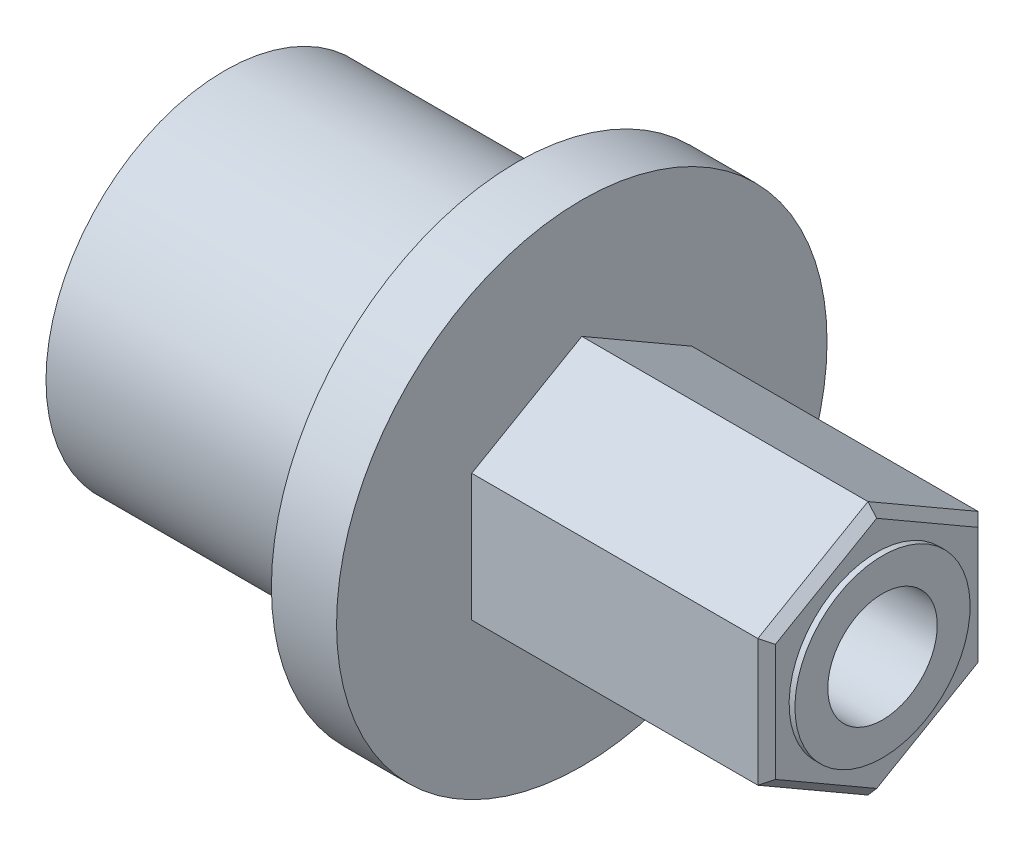
SolidWorks part; units mm, degrees
material "ABS"
ref_plane "Front" through (0, 0, 0) normal (0, 0, 1) x (1, 0, 0)
ref_plane "Top" through (0, 0, 0) normal (0, 1, 0) x (1, 0, 0)
ref_plane "Right" through (0, 0, 0) normal (1, 0, 0) x (0, 0, -1)
ref_axis "side-side" through (80.9, 0, 0) along (-1, 0, 0)
ref_axis "up-down" through (0, 50, 0) along (0, -1, 0)
ref_axis "front-back" through (0, 0, -80.9) along (0, 0, 1)
sketch3d "3DSketch1"
  line L12 (-13.208, 5.4993, 0) -> (-13.208, 2.7496, 4.7625)
  line L13 (-13.208, 2.7496, 4.7625) -> (-13.208, -2.7496, 4.7625)
  line L14 (-13.208, -2.7496, 4.7625) -> (-13.208, -5.4993, 0)
  line L15 (-13.208, -5.4993, 0) -> (-13.208, -2.7496, -4.7625)
  line L16 (-13.208, -2.7496, -4.7625) -> (-13.208, 2.7496, -4.7625)
  line L17 (-13.208, 2.7496, -4.7625) -> (-13.208, 5.4993, 0)
  arc A1 (-13.208, 7.2306, 4.1449) -> (-13.208, 7.4247, 3.7862) centre (-13.208, 0, 0) ccw
  arc A3 (-0.508, 7.2306, 4.1449) -> (-0.508, 7.4247, 3.7862) centre (-0.508, 0, 0) ccw
  point P4 (-21.5424, 0, 0)
  point P9 (-8.8424, 0, 0)
sketch "Sketch1" plane through (0, 0, 0) normal (0, 0, 1) x (1, 0, 0)
  line L0 (-12.8778, 10.668) -> (-12.8778, 3.81)
  line L1 (-12.8778, 3.81) -> (0.2032, 3.81)
  line L3 (0, -50) -> (0, 50) construction
  line L12 (-15.7121, 7.7724) -> (-15.7121, 10.668)
  line L13 (-28.4121, 7.7724) -> (-15.7121, 7.7724)
  line L14 (-28.4121, 7.7724) -> (-28.4121, 6.7564)
  line L15 (-24.037, 2.3812) -> (0.2032, 2.3813)
  line L18 (0.2032, 3.81) -> (0.2032, 2.3813)
  line L19 (-15.7121, 10.668) -> (-12.8778, 10.668)
  line L20 (-22.5988, 0) -> (8.0828, 0) construction
  line L21 (80.9, 0) -> (-80.9, 0) construction
  line L24 (-28.4121, 6.7564) -> (-24.037, 2.3812)
  dimension "D2" = 15.5448
  dimension "D3" = 4.7625
  dimension "D4" = 7.62
  dimension "D5" = 21.336
  dimension "D6" = 13.081
  dimension "D7" = 15.7121
  dimension "D9" = 45
  dimension "D10" = 1.016
  dimension "D13" = 0.2032
  dimension "D14" = 12.7
revolve "Revolve1" add sketch "Sketch1" angle 360 about L20
sketch "Sketch3" plane through (-12.8778, 0, 0) normal (1, 0, 0) x (0, 0, -1)
  line L18 (-4.7879, 2.7643) -> (-4.7879, -2.7643)
  line L19 (-4.7879, -2.7643) -> (0, -5.5286)
  line L20 (0, -5.5286) -> (4.7879, -2.7643)
  line L21 (4.7879, -2.7643) -> (4.7879, 2.7643)
  line L22 (4.7879, 2.7643) -> (0, 5.5286)
  line L23 (0, 5.5286) -> (-4.7879, 2.7643)
  line L24 (-4.7879, 2.7643) -> (-4.7879, -2.7643)
  line L25 (-4.7879, -2.7643) -> (0, -5.5286)
  line L26 (0, -5.5286) -> (4.7879, -2.7643)
  line L27 (4.7879, -2.7643) -> (4.7879, 2.7643)
  line L28 (4.7879, 2.7643) -> (0, 5.5286)
  line L29 (0, 5.5286) -> (-4.7879, 2.7643)
  circle A0 centre (0, 0) radius 3.81 construction
  circle A1 centre (0, 0) radius 3.81
  dimension "D2" = 9.5758
  dimension "D1" = 0.0254
extrude "Boss-Extrude1" add sketch "Sketch3" along normal offset from surface (12.827 mm away) 0.254 up to face at (0.2032, -3.81, 0)
chamfer "Chamfer1" distance 0.381 angle 45 6 edges at (-0.0508, 4.1464, -2.3939) (-0.0508, 0, -4.7879) (-0.0508, -4.1464, -2.394) (-0.0508, -4.1464, 2.3939) (-0.0508, 0, 4.7879) (-0.0508, 4.1464, 2.3939)
